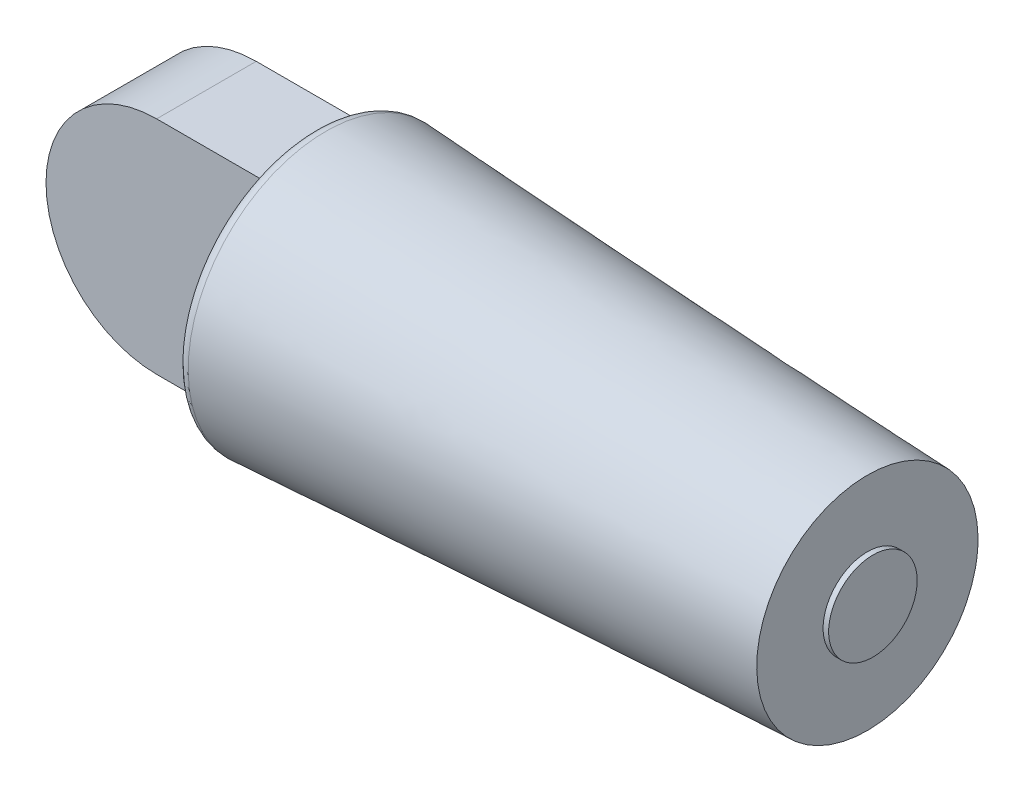
SolidWorks part; units mm, degrees
ref_plane "Front Plane" through (0, 0, 0) normal (0, 0, 1) x (1, 0, 0)
ref_plane "Top Plane" through (0, 0, 0) normal (0, 1, 0) x (1, 0, 0)
ref_plane "Right Plane" through (0, 0, 0) normal (1, 0, 0) x (0, 0, -1)
sketch "Sketch12" plane through (0, 0, 0) normal (1, 0, 0) x (0, 0, -1)
  circle A0 centre (0, 0) radius 125
  dimension "D1" = 250
ref_plane "Plane2" through (500, 0, 0) normal (1, 0, 0) x (0, 0, -1)
sketch "Sketch16" plane through (500, 0, 0) normal (1, 0, 0) x (0, 0, -1)
  circle A0 centre (0, 0) radius 100
  dimension "D1" = 200
loft "Loft5" add profiles "Sketch12", "Sketch16" connector at (0, 9.5725, 124.6329) connector at (500, 33.6372, 94.1729)
sketch "Sketch17" plane through (0, 0, 0) normal (-1, 0, 0) x (0, 0, 1)
  line L0 (-1.6254, 141.7721) -> (-1.6254, -139.6049) construction
  line L1 (-47.6788, 100) -> (42.3212, 100)
  line L2 (-47.6788, 100) -> (-47.6788, -100)
  line L3 (-47.6788, -100) -> (42.3212, -100)
  line L4 (42.3212, 100) -> (42.3212, -100)
  point P6 (-2.6788, 100)
  dimension "D1" = 200
  dimension "D2" = 45
  dimension "D3" = 45
extrude "Boss-Extrude2" add sketch "Sketch17" along normal blind 200
sketch "Sketch21" plane through (0, 0, -47.6788) normal (0, 0, -1) x (-1, 0, 0)
  line L0 (200, 100) -> (0, 100) construction
  line L1 (200, -100) -> (0, -100) construction
  line L2 (100, 100) -> (100, 139.7405)
  line L3 (100, 139.7405) -> (237.0401, 139.7405)
  line L4 (237.0401, 139.7405) -> (237.0401, -127.4422)
  line L5 (237.0401, -127.4422) -> (100, -127.4422)
  line L6 (100, -127.4422) -> (100, -100)
  arc A0 (100, 100) -> (100, -100) centre (100, 0) cw
extrude "Cut-Extrude14" cut sketch "Sketch21" against normal blind 200
fillet "Fillet1" radius 10 1 edges at (0, 0, -125) type face fillet first side face at (0, 0, -125) second side face at (0, 0, -125)
sketch "Sketch22" plane through (500, 0, 0) normal (1, 0, 0) x (0, 0, -1)
  circle A0 centre (0, 0) radius 40
  dimension "D1" = 80
extrude "Boss-Extrude3" add sketch "Sketch22" along normal blind 5
